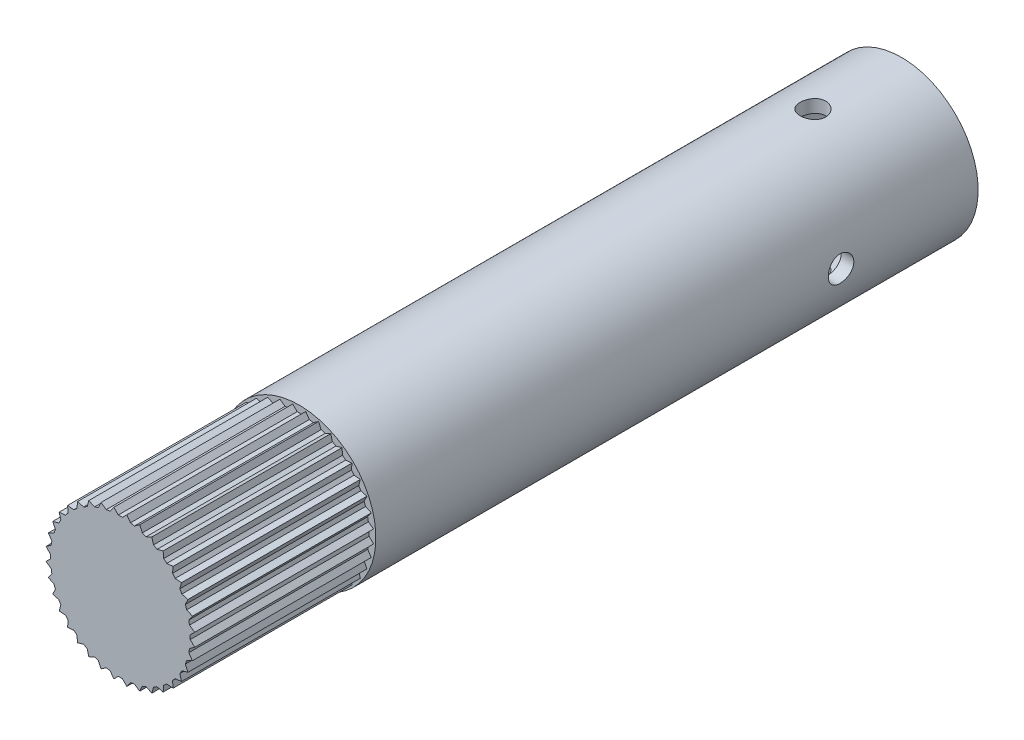
SolidWorks part; units mm, degrees
material "AISI 1015 Steel, Cold Drawn (SS)"
ref_plane "X-Y Datum" through (0, 0, 0) normal (0, 0, 1) x (1, 0, 0)
ref_plane "X-Z Datum" through (0, 0, 0) normal (0, 1, 0) x (1, 0, 0)
ref_plane "Y-Z Datum" through (0, 0, 0) normal (1, 0, 0) x (0, 0, -1)
sketch "Sketch9" plane through (0, 0, 0) normal (0, 1, 0) x (1, 0, 0)
  line L0 (16.002, 0) -> (0, 0)
  line L1 (0, 0) -> (0, -389.0916)
  line L2 (0, -389.0916) -> (-72.2493, -524.9728)
  dimension "D1" = 153.895
  dimension "D2" = 28
  dimension "D3" = 389.0916
  dimension "D5" = 16.002
sketch "Sketch5" plane through (0, 0, 0) normal (0, 1, 0) x (1, 0, 0)
  line L0 (7.9375, -119.2166) -> (7.9375, -22.1615)
  line L1 (7.9375, -22.1615) -> (9.525, -22.1615)
  line L2 (9.525, -22.1615) -> (9.525, -119.2166)
  line L3 (9.525, -119.2166) -> (7.9375, -119.2166)
  line L5 (16.002, 0) -> (0, 0) construction
  line L6 (0, 0) -> (0, -389.0916) construction
  line L7 (0, -389.0916) -> (9.525, -389.0916) construction
  line L8 (12.5602, -99.9666) -> (0, -99.9666) construction
  dimension "D1" = 1.5875
  dimension "D2" = 22.1615
  dimension "D3" = 7.9375
  dimension "D4" = 289.125
  dimension "D5" = 269.875
revolve "Revolve2" add sketch "Sketch5" angle 360 about L1
sketch "Sketch6" plane through (0, 0, 0) normal (0, 1, 0) x (1, 0, 0)
  circle A0 centre (0, -33.1635) radius 1.5875 construction
  circle A1 centre (0, -33.1635) radius 1.5875
sketch "Sketch7" plane through (0, 0, 0) normal (1, 0, 0) x (0, 0, -1)
  circle A2 centre (-39.196, 0) radius 1.5875
  circle A4 centre (-39.196, 0) radius 1.5875 construction
extrude "Cut-Extrude5" cut sketch "Sketch7" against normal through all both and the other way through all
extrude "Cut-Extrude6" cut sketch "Sketch6" against normal through all both and the other way through all
sketch "Sketch8" plane through (0, 0, 0) normal (0, 0, 1) x (1, 0, 0)
  line L0 (9.2357, -0.808) -> (8.6817, -0.254)
  line L1 (8.6817, -0.254) -> (8.6817, 0.254)
  line L2 (8.6817, 0.254) -> (9.2357, 0.808)
  line L3 (8.6817, 0) -> (0, 0) construction
  line L4 (8.9551, -2.3995) -> (8.5057, -1.7577)
  line L5 (8.5057, -1.7577) -> (8.5939, -1.2574)
  line L6 (8.5939, -1.2574) -> (9.2357, -0.808)
  line L7 (8.4024, -3.9181) -> (8.0713, -3.208)
  line L8 (8.0713, -3.208) -> (8.245, -2.7306)
  line L9 (8.245, -2.7306) -> (8.9551, -2.3995)
  line L10 (7.5944, -5.3176) -> (7.3916, -4.5608)
  line L11 (7.3916, -4.5608) -> (7.6456, -4.1209)
  line L12 (7.6456, -4.1209) -> (8.4024, -3.9181)
  line L13 (6.5556, -6.5556) -> (6.4873, -5.7751)
  line L14 (6.4873, -5.7751) -> (6.8138, -5.3859)
  line L15 (6.8138, -5.3859) -> (7.5944, -5.3176)
  line L16 (5.3176, -7.5944) -> (5.3859, -6.8138)
  line L17 (5.3859, -6.8138) -> (5.7751, -6.4873)
  line L18 (5.7751, -6.4873) -> (6.5556, -6.5556)
  line L19 (3.9181, -8.4024) -> (4.1209, -7.6456)
  line L20 (4.1209, -7.6456) -> (4.5608, -7.3916)
  line L21 (4.5608, -7.3916) -> (5.3176, -7.5944)
  line L22 (2.3995, -8.9551) -> (2.7306, -8.245)
  line L23 (2.7306, -8.245) -> (3.208, -8.0713)
  line L24 (3.208, -8.0713) -> (3.9181, -8.4024)
  line L25 (0.808, -9.2357) -> (1.2574, -8.5939)
  line L26 (1.2574, -8.5939) -> (1.7577, -8.5057)
  line L27 (1.7577, -8.5057) -> (2.3995, -8.9551)
  line L28 (-0.808, -9.2357) -> (-0.254, -8.6817)
  line L29 (-0.254, -8.6817) -> (0.254, -8.6817)
  line L30 (0.254, -8.6817) -> (0.808, -9.2357)
  line L31 (-2.3995, -8.9551) -> (-1.7577, -8.5057)
  line L32 (-1.7577, -8.5057) -> (-1.2574, -8.5939)
  line L33 (-1.2574, -8.5939) -> (-0.808, -9.2357)
  line L34 (-3.9181, -8.4024) -> (-3.208, -8.0713)
  line L35 (-3.208, -8.0713) -> (-2.7306, -8.245)
  line L36 (-2.7306, -8.245) -> (-2.3995, -8.9551)
  line L37 (-5.3176, -7.5944) -> (-4.5608, -7.3916)
  line L38 (-4.5608, -7.3916) -> (-4.1209, -7.6456)
  line L39 (-4.1209, -7.6456) -> (-3.9181, -8.4024)
  line L40 (-6.5556, -6.5556) -> (-5.7751, -6.4873)
  line L41 (-5.7751, -6.4873) -> (-5.3859, -6.8138)
  line L42 (-5.3859, -6.8138) -> (-5.3176, -7.5944)
  line L43 (-7.5944, -5.3176) -> (-6.8138, -5.3859)
  line L44 (-6.8138, -5.3859) -> (-6.4873, -5.7751)
  line L45 (-6.4873, -5.7751) -> (-6.5556, -6.5556)
  line L46 (-8.4024, -3.9181) -> (-7.6456, -4.1209)
  line L47 (-7.6456, -4.1209) -> (-7.3916, -4.5608)
  line L48 (-7.3916, -4.5608) -> (-7.5944, -5.3176)
  line L49 (-8.9551, -2.3995) -> (-8.245, -2.7306)
  line L50 (-8.245, -2.7306) -> (-8.0713, -3.208)
  line L51 (-8.0713, -3.208) -> (-8.4024, -3.9181)
  line L52 (-9.2357, -0.808) -> (-8.5939, -1.2574)
  line L53 (-8.5939, -1.2574) -> (-8.5057, -1.7577)
  line L54 (-8.5057, -1.7577) -> (-8.9551, -2.3995)
  line L55 (-9.2357, 0.808) -> (-8.6817, 0.254)
  line L56 (-8.6817, 0.254) -> (-8.6817, -0.254)
  line L57 (-8.6817, -0.254) -> (-9.2357, -0.808)
  line L58 (-8.9551, 2.3995) -> (-8.5057, 1.7577)
  line L59 (-8.5057, 1.7577) -> (-8.5939, 1.2574)
  line L60 (-8.5939, 1.2574) -> (-9.2357, 0.808)
  line L61 (-8.4024, 3.9181) -> (-8.0713, 3.208)
  line L62 (-8.0713, 3.208) -> (-8.245, 2.7306)
  line L63 (-8.245, 2.7306) -> (-8.9551, 2.3995)
  line L64 (-7.5944, 5.3176) -> (-7.3916, 4.5608)
  line L65 (-7.3916, 4.5608) -> (-7.6456, 4.1209)
  line L66 (-7.6456, 4.1209) -> (-8.4024, 3.9181)
  line L67 (-6.5556, 6.5556) -> (-6.4873, 5.7751)
  line L68 (-6.4873, 5.7751) -> (-6.8138, 5.3859)
  line L69 (-6.8138, 5.3859) -> (-7.5944, 5.3176)
  line L70 (-5.3176, 7.5944) -> (-5.3859, 6.8138)
  line L71 (-5.3859, 6.8138) -> (-5.7751, 6.4873)
  line L72 (-5.7751, 6.4873) -> (-6.5556, 6.5556)
  line L73 (-3.9181, 8.4024) -> (-4.1209, 7.6456)
  line L74 (-4.1209, 7.6456) -> (-4.5608, 7.3916)
  line L75 (-4.5608, 7.3916) -> (-5.3176, 7.5944)
  line L76 (-2.3995, 8.9551) -> (-2.7306, 8.245)
  line L77 (-2.7306, 8.245) -> (-3.208, 8.0713)
  line L78 (-3.208, 8.0713) -> (-3.9181, 8.4024)
  line L79 (-0.808, 9.2357) -> (-1.2574, 8.5939)
  line L80 (-1.2574, 8.5939) -> (-1.7577, 8.5057)
  line L81 (-1.7577, 8.5057) -> (-2.3995, 8.9551)
  line L82 (0.808, 9.2357) -> (0.254, 8.6817)
  line L83 (0.254, 8.6817) -> (-0.254, 8.6817)
  line L84 (-0.254, 8.6817) -> (-0.808, 9.2357)
  line L85 (2.3995, 8.9551) -> (1.7577, 8.5057)
  line L86 (1.7577, 8.5057) -> (1.2574, 8.5939)
  line L87 (1.2574, 8.5939) -> (0.808, 9.2357)
  line L88 (3.9181, 8.4024) -> (3.208, 8.0713)
  line L89 (3.208, 8.0713) -> (2.7306, 8.245)
  line L90 (2.7306, 8.245) -> (2.3995, 8.9551)
  line L91 (5.3176, 7.5944) -> (4.5608, 7.3916)
  line L92 (4.5608, 7.3916) -> (4.1209, 7.6456)
  line L93 (4.1209, 7.6456) -> (3.9181, 8.4024)
  line L94 (6.5556, 6.5556) -> (5.7751, 6.4873)
  line L95 (5.7751, 6.4873) -> (5.3859, 6.8138)
  line L96 (5.3859, 6.8138) -> (5.3176, 7.5944)
  line L97 (7.5944, 5.3176) -> (6.8138, 5.3859)
  line L98 (6.8138, 5.3859) -> (6.4873, 5.7751)
  line L99 (6.4873, 5.7751) -> (6.5556, 6.5556)
  line L100 (8.4024, 3.9181) -> (7.6456, 4.1209)
  line L101 (7.6456, 4.1209) -> (7.3916, 4.5608)
  line L102 (7.3916, 4.5608) -> (7.5944, 5.3176)
  line L103 (8.9551, 2.3995) -> (8.245, 2.7306)
  line L104 (8.245, 2.7306) -> (8.0713, 3.208)
  line L105 (8.0713, 3.208) -> (8.4024, 3.9181)
  line L106 (9.2357, 0.808) -> (8.5939, 1.2574)
  line L107 (8.5939, 1.2574) -> (8.5057, 1.7577)
  line L108 (8.5057, 1.7577) -> (8.9551, 2.3995)
  circle A0 centre (0, 0) radius 12.7
  circle A1 centre (0, 0) radius 9.271 construction
  circle A2 centre (0, 0) radius 8.6854 construction
  point P153 (0, 0)
  dimension "D1" = 25.4
  dimension "D4" = 18.542
  dimension "D6" = 17.3708
  dimension "D2" = 0.508
  dimension "D3" = 135
  dimension "D5" = 36
extrude "Cut-Extrude7" cut sketch "Sketch8" against normal blind 22.225 from surface starting at face at (-9.525, 0, 119.2166)
ref_plane "Plane1" through (0, 0, 47.5615) normal (0, 0, -1) x (-1, 0, 0)
sketch "Sketch10" plane through (0, 0, 47.5615) normal (0, 0, -1) x (-1, 0, 0)
  circle A0 centre (0, 0) radius 7.9375
  dimension "D1" = 15.875
extrude "Boss-Extrude1" add sketch "Sketch10" against normal up to surface (71.6551 mm away) up to face at (-7.9375, 0, 119.2166)
sketch "Sketch11" plane through (0, 0, 22.1615) normal (0, 0, -1) x (-1, 0, 0)
  line L0 (0, 9.525) -> (13.3548, 9.525) construction
  line L1 (0, 9.525) -> (0, 15.4312) construction
  line L2 (-9.525, 0) -> (-9.525, 9.1744) construction
  line L3 (-9.525, 0) -> (-16.674, 0) construction
  circle A0 centre (0, 0) radius 9.525 construction
  point P0 (0, 9.525)
  point P1 (-9.525, 0)
